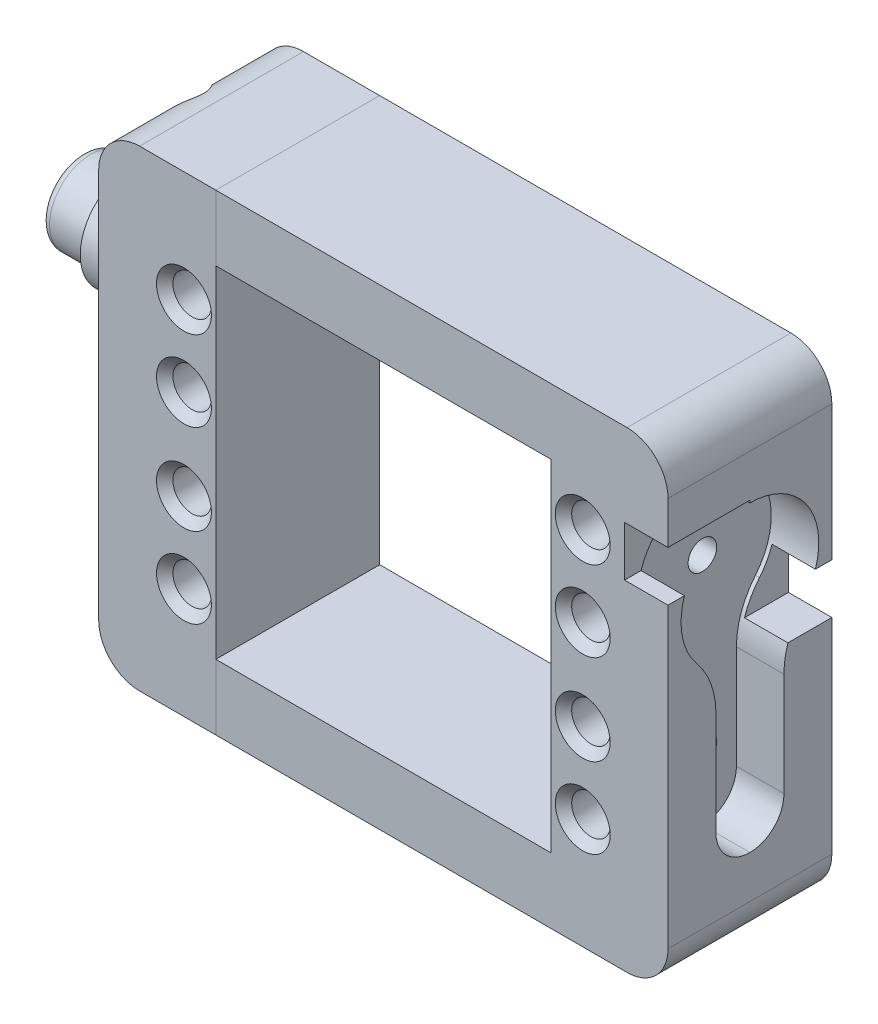
SolidWorks part; units mm, degrees
material "ABS"
ref_plane "Front Plane" through (0, 0, 0) normal (0, 0, 1) x (1, 0, 0)
ref_plane "Top Plane" through (0, 0, 0) normal (0, 1, 0) x (1, 0, 0)
ref_plane "Right Plane" through (0, 0, 0) normal (1, 0, 0) x (0, 0, -1)
sketch "Sketch1" plane through (0, 0, 0) normal (1, 0, 0) x (0, 0, -1)
  line L1 (-10, 10) -> (10, 10)
  line L2 (-10, 10) -> (-10, -10)
  line L3 (-10, -10) -> (10, -10)
  line L4 (10, 10) -> (10, -10)
  line L5 (-10, 10) -> (10, -10) construction
  line L6 (-10, -10) -> (10, 10) construction
  point P0 (0, 0)
  dimension "D1" = 20
  dimension "D2" = 20
extrude "Boss-Extrude1" add sketch "Sketch1" along normal blind 20
sketch "Sketch2" plane through (20, 0, 0) normal (1, 0, 0) x (0, 0, -1)
  line L1 (-10, 35) -> (10, 35)
  line L2 (-10, 35) -> (-10, -35)
  line L3 (-10, -35) -> (10, -35)
  line L4 (10, 35) -> (10, -35)
  line L5 (-10, 35) -> (10, -35) construction
  line L6 (-10, -35) -> (10, 35) construction
  point P0 (0, 0)
  dimension "D1" = 20
  dimension "D2" = 70
extrude "Boss-Extrude2" add sketch "Sketch2" along normal blind 10.3
sketch "Sketch4" plane through (30.3, 0, 0) normal (1, 0, 0) x (0, 0, -1)
  line L0 (0, 7.65) -> (0, 8.1702) construction
  line L1 (7.65, 7.65) -> (-7.65, 7.65) construction
  line L17 (4.15, -26.55) -> (-4.15, -26.55) construction
  line L18 (-7.65, 7.65) -> (7.65, 7.65) construction
  line L22 (-7.65, 7.65) -> (-7.65, -27.55) construction
  line L23 (-7.65, -27.55) -> (7.65, -27.55) construction
  line L24 (7.65, 7.65) -> (7.65, -27.55) construction
  line L25 (-7.65, 7.65) -> (7.65, -27.55) construction
  line L26 (-7.65, -27.55) -> (7.65, 7.65) construction
  line L27 (4.15, -26.55) -> (4.15, -28.55) construction
  line L28 (4.15, -28.55) -> (-4.15, -28.55) construction
  line L29 (-4.15, -26.55) -> (-4.15, -28.55) construction
  line L30 (4.15, -26.55) -> (-4.15, -28.55) construction
  line L31 (4.15, -28.55) -> (-4.15, -26.55) construction
  line L34 (4.15, -28.55) -> (-4.15, -28.55)
  line L35 (-4.15, -28.55) -> (-4.15, -7.3118)
  line L36 (4.15, -28.55) -> (4.15, -7.3118)
  arc A1 (4.15, -6.4265) -> (-4.15, -6.4265) centre (0, 0) ccw construction
  arc A2 (4.15, -7.3118) -> (-4.15, -7.3118) centre (0, 0) ccw
  point P1 (0, -27.55)
  point P7 (0, -13.75)
  point P10 (0, 7.65)
  point P14 (0, -9.95)
  dimension "D1" = 15.3
  dimension "D5" = 2
  dimension "D2" = 15.3
  dimension "D3" = 35.2
  dimension "D4" = 8.3
extrude "Cut-Extrude1" cut sketch "Sketch4" against normal blind 5.8
fillet "Fillet1" radius 4.15 2 edges at (27.4, -28.55, 4.15) (27.4, -28.55, -4.15)
fillet "Fillet2" radius 10 2 edges at (27.4, -7.3118, 4.15) (27.4, -7.3118, -4.15)
sketch "Sketch5" plane through (0, 0, 0) normal (-1, 0, 0) x (0, 0, 1)
  circle A0 centre (0, 0) radius 1.75
  dimension "D1" = 3.5
extrude "Cut-Extrude2" cut sketch "Sketch5" against normal through all
sketch "Sketch6" plane through (24.5, 0, 0) normal (1, 0, 0) x (0, 0, -1)
  line L0 (0, -19.35) -> (0, 0) construction
  line L1 (0, -25.65) -> (0, -23.15) construction
  line L2 (0, -23.15) -> (0, -21.85) construction
  line L3 (0, -21.85) -> (0, -19.35) construction
  line L5 (0, 0) -> (1.164, 0) construction
  line L6 (0, 0) -> (0, -9.35) construction
  line L7 (0, -9.35) -> (1.164, -9.35) construction
  line L8 (1.164, 0) -> (1.164, -9.35) construction
  line L9 (0, 0) -> (1.164, -9.35) construction
  line L10 (0, -9.35) -> (1.164, 0) construction
  circle A0 centre (0, -20.6) radius 1.75
  circle A1 centre (0, -9.35) radius 1.75 construction
  point P11 (0.582, -4.675)
  dimension "D5" = 3.5
  dimension "D6" = 9.35
  dimension "D7" = 3.5
  dimension "D1" = 19.35
  dimension "D2" = 2.5
  dimension "D3" = 1.3
  dimension "D4" = 2.5
extrude "Cut-Extrude3" cut sketch "Sketch6" against normal up to next
sketch "Sketch13" plane through (0, 0, 0) normal (-1, 0, 0) x (0, 0, 1)
  line L1 (-10, 10) -> (10, 10)
  line L2 (-10, 10) -> (-10, -10)
  line L3 (-10, -10) -> (10, -10)
  line L4 (10, 10) -> (10, -10)
extrude "Cut-Extrude9" cut sketch "Sketch13" against normal up to surface (20 mm away) up to face at (20, 22.5, 0)
sketch "Sketch29" plane through (30.3, 0, 0) normal (1, 0, 0) x (0, 0, -1)
  line L0 (0, 0) -> (0, 2.6) construction
  line L1 (15.1094, -8.7) -> (15.1094, -2.6)
  line L2 (0, 2.6) -> (-15.1094, 2.6)
  line L4 (0, 2.6) -> (0, 3.8)
  line L5 (0, 3.8) -> (0, 7.5)
  line L6 (0, 7.5) -> (0, 8.7)
  line L7 (0, 8.7) -> (-15.1094, 8.7)
  line L8 (-15.1094, 8.7) -> (-15.1094, 2.6)
  line L9 (0, -2.6) -> (15.1094, -2.6)
  line L10 (0, -2.6) -> (0, -3.8)
  line L11 (0, -3.8) -> (0, -7.5)
  line L12 (0, -7.5) -> (0, -8.7)
  line L13 (0, -8.7) -> (15.1094, -8.7)
  point P19 (0, 0)
  dimension "D1" = 2.6
  dimension "D2" = 1.2
  dimension "D3" = 3.7
  dimension "D4" = 1.2
  dimension "D5" = 2
extrude "Cut-Extrude18" cut sketch "Sketch29" against normal blind 5.3
sketch "Sketch32" plane through (30.3, 0, 0) normal (1, 0, 0) x (0, 0, -1)
  line L0 (0, -28.55) -> (0, -38.725) construction
  line L1 (10, -35) -> (10, -8.7) construction
  line L2 (-10, -35) -> (10, -35)
  line L3 (-10, -35) -> (-10, -38.725)
  line L4 (-10, -38.725) -> (10, -38.725)
  line L5 (10, -35) -> (10, -38.725)
  dimension "D1" = 10.175
extrude "Boss-Extrude3" add sketch "Sketch32" against normal up to surface (10.3 mm away) up to face at (20, 0, 0)
sketch "Sketch31" plane through (30.3, 0, 0) normal (1, 0, 0) x (0, 0, -1)
  line L2 (0, 8.7) -> (0, 18.875) construction
  line L3 (10, -2.6) -> (10, 35) construction
  line L4 (-10, 35) -> (10, 35)
  line L5 (-10, 35) -> (-10, 18.875)
  line L6 (-10, 18.875) -> (10, 18.875)
  line L7 (10, 35) -> (10, 18.875)
  dimension "D1" = 10.175
extrude "Cut-Extrude19" cut sketch "Sketch31" against normal through all
sketch "Sketch34" plane through (20, 0, 0) normal (-1, 0, 0) x (0, 0, 1)
  line L4 (10, -38.725) -> (10, 18.875)
  line L5 (10, 18.875) -> (-10, 18.875)
  line L6 (-10, 18.875) -> (-10, -38.725)
  line L7 (-10, -38.725) -> (10, -38.725)
  line L8 (10, -38.725) -> (10, 18.875)
  line L9 (10, 18.875) -> (-10, 18.875)
  line L10 (-10, 18.875) -> (-10, -38.725)
  line L11 (-10, -38.725) -> (10, -38.725)
  circle A0 centre (0, -20.6) radius 1.75 construction
  circle A1 centre (0, 0) radius 1.75 construction
  circle A2 centre (0, -20.6) radius 1.75
  circle A3 centre (0, 0) radius 1.75
  dimension "D1" = 0
extrude "Boss-Extrude5" add sketch "Sketch34" along normal blind 4
sketch "Sketch35" plane through (16, 0, 0) normal (-1, 0, 0) x (0, 0, 1)
  line L0 (10, -38.725) -> (10, 18.875) construction
  line L1 (-10, 18.875) -> (10, 18.875)
  line L2 (-10, 18.875) -> (-10, 10.875)
  line L3 (-10, 10.875) -> (10, 10.875)
  line L4 (10, 18.875) -> (10, 10.875)
  line L5 (0, 10.875) -> (0, -30.725) construction
  line L6 (-10, -38.725) -> (10, -38.725)
  line L7 (-10, -38.725) -> (-10, -30.725)
  line L8 (-10, -30.725) -> (10, -30.725)
  line L9 (10, -38.725) -> (10, -30.725)
  dimension "D1" = 41.6
extrude "Boss-Extrude6" add sketch "Sketch35" along normal blind 40.9
sketch "Sketch37" plane through (-24.9, 0, 0) normal (-1, 0, 0) x (0, 0, 1)
  line L1 (-10, 18.875) -> (10, 18.875)
  line L2 (-10, 18.875) -> (-10, -38.725)
  line L3 (-10, -38.725) -> (10, -38.725)
  line L4 (10, 18.875) -> (10, -38.725)
extrude "Boss-Extrude7" add sketch "Sketch37" along normal blind 14.3
sketch "Sketch38" plane through (0, 0, 10) normal (0, 0, 1) x (1, 0, 0)
  line L0 (-24.9, 10.875) -> (-24.9, -9.925) construction
  line L1 (-24.9, -9.925) -> (-24.9, -30.725) construction
  line L2 (-24.9, -30.725) -> (-24.9, 10.875) construction
  line L3 (-24.9, -9.925) -> (-39.2, -9.925) construction
  line L4 (-39.2, -38.725) -> (-39.2, 18.875) construction
  line L5 (-24.9, 0.475) -> (-28.79, 0.475) construction
  line L6 (-28.79, 0.475) -> (-28.79, 5.375) construction
  line L7 (-24.9, 10.875) -> (16, 10.875) construction
  line L8 (-4.45, 10.875) -> (-4.45, -38.725) construction
  line L9 (-39.2, -38.725) -> (30.3, -38.725) construction
  circle A0 centre (-28.79, 5.375) radius 2.35
  circle A1 centre (-28.79, -4.425) radius 2.35
  circle A2 centre (-28.79, -25.225) radius 2.35
  circle A3 centre (-28.79, -15.425) radius 2.35
  circle A4 centre (19.89, 5.375) radius 2.35
  circle A5 centre (19.89, -4.425) radius 2.35
  circle A6 centre (19.89, -15.425) radius 2.35
  circle A7 centre (19.89, -25.225) radius 2.35
  dimension "D4" = 4.7
  dimension "D1" = 41.6
  dimension "D2" = 3.89
  dimension "D3" = 4.9
extrude "Cut-Extrude20" cut sketch "Sketch38" against normal blind 8
chamfer "Chamfer1" distance 1 angle 45 8 edges at (22.24, -25.225, 10) (17.54, -15.425, 10) (22.24, -4.425, 10) (17.54, 5.375, 10) (-26.44, 5.375, 10) (-26.44, -15.425, 10) (-31.14, -25.225, 10) (-31.14, -4.425, 10)
sketch "Sketch41" plane through (16, 0, 0) normal (-1, 0, 0) x (0, 0, 1)
  circle A0 centre (0, 0) radius 3.5
  circle A1 centre (0, -20.6) radius 3.5
  dimension "D1" = 7
  dimension "D2" = 7
extrude "Cut-Extrude23" cut sketch "Sketch41" against normal blind 4
sketch "Sketch42" plane through (-39.2, 0, 0) normal (-1, 0, 0) x (0, 0, 1)
  line L0 (10, -38.725) -> (10, 18.875) construction
  line L1 (-10, -38.725) -> (10, -38.725) construction
  line L2 (-10, -38.725) -> (-10, -30.725) construction
  line L3 (-10, -30.725) -> (10, -30.725) construction
  line L4 (10, -38.725) -> (10, -30.725) construction
  line L5 (-10, -9.925) -> (10, -9.925) construction
  line L6 (-10, 18.875) -> (-10, -38.725) construction
  circle A0 centre (0, -34.725) radius 1.75
  circle A1 centre (0, 14.875) radius 1.75
  point P9 (-10, -34.725)
  dimension "D2" = 3.5
  dimension "D1" = 8
  dimension "D3" = 4
  dimension "D4" = 10
extrude "Cut-Extrude24" cut sketch "Sketch42" against normal blind 22.3
sketch "Sketch43" plane through (-39.2, 0, 0) normal (-1, 0, 0) x (0, 0, 1)
  circle A0 centre (0, 14.875) radius 3.5
  circle A1 centre (0, -34.725) radius 3.5
  dimension "D1" = 7
  dimension "D2" = 7
extrude "Cut-Extrude25" cut sketch "Sketch43" against normal blind 11
fillet "Fillet3" radius 5 4 edges at (-39.2, -38.725, 0) (30.3, -38.725, 0) (30.3, 18.875, 0) (-39.2, 18.875, 0)
sketch "Sketch44" plane through (0, 0, 10) normal (0, 0, 1) x (1, 0, 0)
  line L0 (-24.9, 18.875) -> (-24.9, -38.725)
  line L1 (-34.2, 18.875) -> (25.3, 18.875) construction
  line L2 (-34.2, -38.725) -> (25.3, -38.725) construction
split "Split1" trim tools "Sketch44" bodies to split 171 resulting bodies 172 173
sketch "Sketch45" plane through (-24.9, 0, 0) normal (-1, 0, 0) x (0, 0, 1)
  circle A0 centre (0, 14.875) radius 2.35
  circle A1 centre (0, -34.725) radius 2.35
  dimension "D1" = 4.7
  dimension "D2" = 4.7
extrude "Cut-Extrude26" cut sketch "Sketch45" against normal blind 8
chamfer "Chamfer2" distance 1 angle 45 2 edges at (-24.9, -34.725, 2.35) (-24.9, 14.875, 2.35)
sketch "Sketch46" plane through (-39.2, 0, 0) normal (-1, 0, 0) x (0, 0, 1)
  circle A1 centre (0, 0) radius 5
  dimension "D1" = 10
extrude "Boss-Extrude8" add sketch "Sketch46" along normal blind 12
fillet "Fillet5" radius 1 1 edges at (-51.2, 0, 5)
mirror "Mirror1" [suppressed] of bodies 177 174 167 172 173
delete or keep bodies "Body-Delete/Keep 1" [suppressed] type delete bodies bodies 177 174
sketch "Sketch47" plane through (0, 0, 10) normal (0, 0, 1) x (1, 0, 0)
  line L0 (19.89, 5.375) -> (19.89, -4.425)
  line L1 (19.89, 0.475) -> (28.8988, 0.475)
sketch "Sketch48" plane through (24.5, 0, 0) normal (1, 0, 0) x (0, 0, -1)
  line L0 (0, 0) -> (-13.129, 0)
  line L1 (-10, 8.725) -> (-10, 2.025) construction
sketch "Sketch49" plane through (0, 0, 10) normal (0, 0, 1) x (1, 0, 0)
  line L0 (24.5491, 0) -> (24.5491, 0.475)
  line L1 (19.89, 0.475) -> (28.8988, 0.475) construction
sketch "Sketch50" plane through (-39.2, 0, 0) normal (-1, 0, 0) x (0, 0, 1)
  circle A0 centre (0, 0) radius 6.25
  dimension "D1" = 12.5
extrude "Boss-Extrude9" add sketch "Sketch50" along normal blind 6
fillet "Fillet6" radius 3 1 edges at (-39.2, 0, 6.25)
